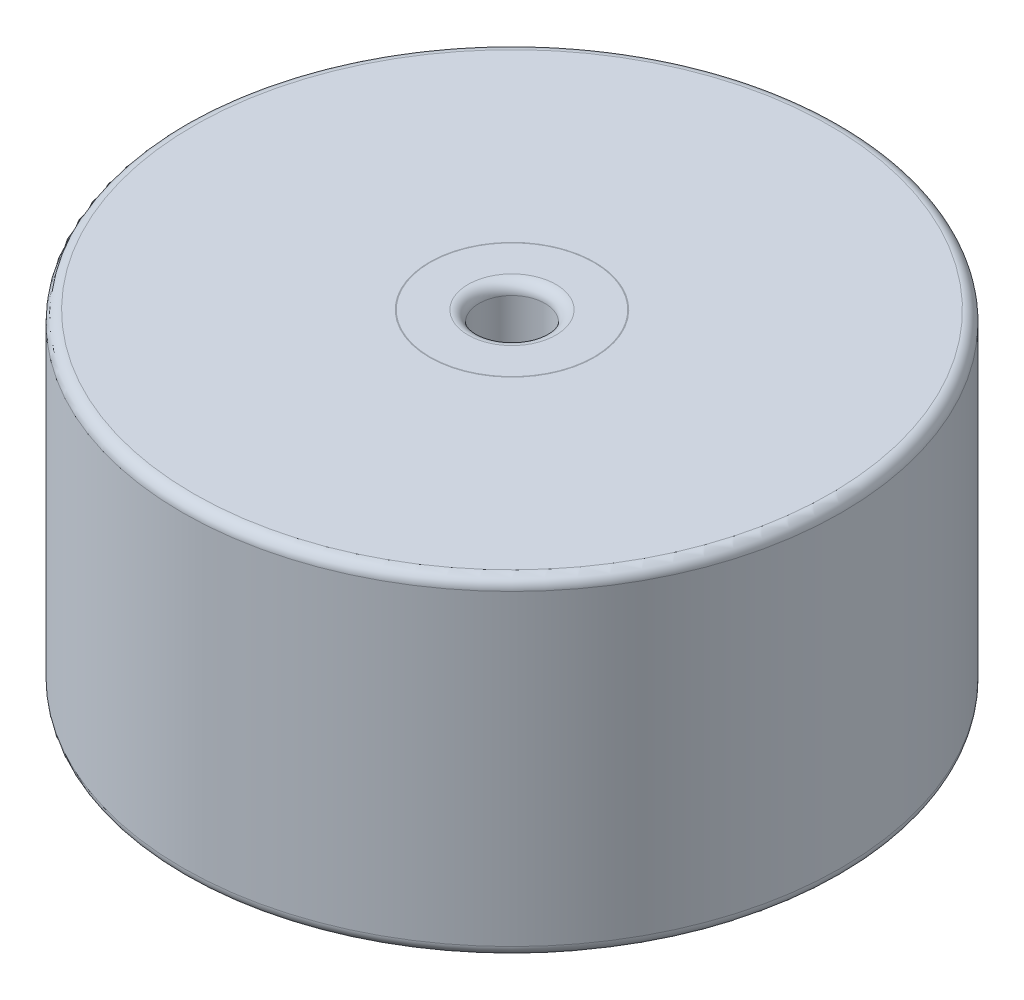
SolidWorks part; units mm, degrees
material "Rubber"
ref_plane "Front Plane" through (0, 0, 0) normal (0, 0, 1) x (1, 0, 0)
ref_plane "Top Plane" through (0, 0, 0) normal (0, 1, 0) x (1, 0, 0)
ref_plane "Right Plane" through (0, 0, 0) normal (1, 0, 0) x (0, 0, -1)
sketch "Sketch1" plane through (0, 0, 0) normal (0, 1, 0) x (1, 0, 0)
  circle A0 centre (0, 0) radius 300
  circle A3 centre (0, 0) radius 75
  dimension "D1" = 600
  dimension "D2" = 150
extrude "Boss-Extrude2" add sketch "Sketch1" along normal blind 300
sketch "Sketch2" plane through (0, 300, 0) normal (0, 1, 0) x (1, 0, 0)
  circle A0 centre (0, 0) radius 75
extrude "Boss-Extrude3" add sketch "Sketch2" along normal blind 0.01 and the other way blind 300
sketch "Sketch3" plane through (0, 300.01, 0) normal (0, 1, 0) x (1, 0, 0)
  circle A0 centre (0, 0) radius 30
  dimension "D1" = 60
extrude "Cut-Extrude1" cut sketch "Sketch3" against normal through all both and the other way through all
fillet "Fillet1" radius 10 4 edges at (0, 300.01, 75) (0, 300.01, 30) (0, 0, 300) (0, 300, 300)
fillet "Fillet2" radius 10 1 edges at (0, 300, 75)
fillet "Fillet3" radius 10 1 edges at (0, 0, 30)
